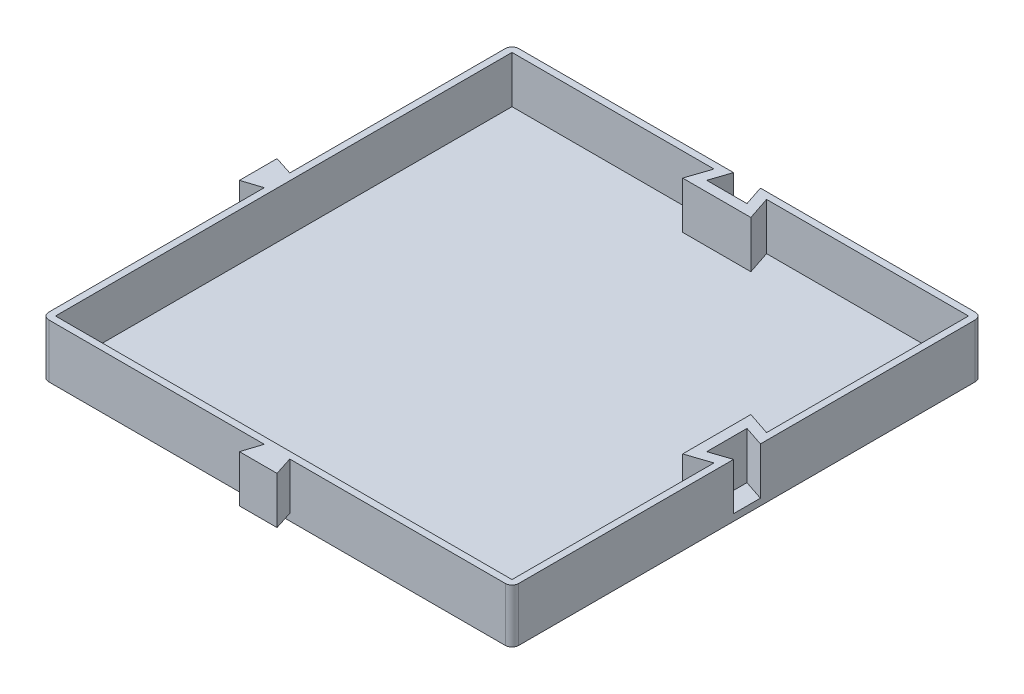
SolidWorks part; units mm, degrees
ref_plane "Front Plane" through (0, 0, 0) normal (0, 0, 1) x (1, 0, 0)
ref_plane "Top Plane" through (0, 0, 0) normal (0, 1, 0) x (1, 0, 0)
ref_plane "Right Plane" through (0, 0, 0) normal (1, 0, 0) x (0, 0, -1)
sketch "Sketch1" plane through (0, 0, 0) normal (0, 1, 0) x (1, 0, 0)
  line L1 (0, 0) -> (88.9, 0)
  line L2 (0, 0) -> (0, 88.9)
  line L3 (0, 88.9) -> (88.9, 88.9)
  line L4 (88.9, 0) -> (88.9, 88.9)
  dimension "D1" = 88.9
  dimension "D2" = 88.9
extrude "Base/Drain Tray" add sketch "Sketch1" along normal blind 10.16
sketch "Sketch2" plane through (0, 10.16, 0) normal (0, 1, 0) x (1, 0, 0)
  line L8 (1.27, 87.63) -> (1.27, 1.27)
  line L9 (1.27, 1.27) -> (87.63, 1.27)
  line L10 (87.63, 1.27) -> (87.63, 87.63)
  line L11 (87.63, 87.63) -> (1.27, 87.63)
  line L12 (1.27, 87.63) -> (1.27, 1.27)
  line L13 (1.27, 1.27) -> (87.63, 1.27)
  line L14 (87.63, 1.27) -> (87.63, 87.63)
  line L15 (87.63, 87.63) -> (1.27, 87.63)
  dimension "D1" = 1.27
extrude "Drain Tray Cutout" cut sketch "Sketch2" against normal blind 8.89
sketch "Sketch3" plane through (0, 1.27, 0) normal (0, 1, 0) x (1, 0, 0)
  line L8 (80.01, 80.01) -> (8.89, 80.01)
  line L9 (8.89, 80.01) -> (8.89, 8.89)
  line L10 (8.89, 8.89) -> (80.01, 8.89)
  line L11 (80.01, 8.89) -> (80.01, 80.01)
  line L12 (80.01, 80.01) -> (8.89, 80.01)
  line L13 (8.89, 80.01) -> (8.89, 8.89)
  line L14 (8.89, 8.89) -> (80.01, 8.89)
  line L15 (80.01, 8.89) -> (80.01, 80.01)
  dimension "D2" = 71.12
  dimension "D1" = 7.62
extrude "Body" add sketch "Sketch3" along normal blind 50.8
sketch "Sketch4" plane through (0, 52.07, 0) normal (0, 1, 0) x (1, 0, 0)
  line L8 (78.74, 10.16) -> (78.74, 78.74)
  line L9 (78.74, 78.74) -> (10.16, 78.74)
  line L10 (10.16, 78.74) -> (10.16, 10.16)
  line L11 (10.16, 10.16) -> (78.74, 10.16)
  line L12 (78.74, 10.16) -> (78.74, 78.74)
  line L13 (78.74, 78.74) -> (10.16, 78.74)
  line L14 (10.16, 78.74) -> (10.16, 10.16)
  line L15 (10.16, 10.16) -> (78.74, 10.16)
  dimension "D1" = 1.27
extrude "Body Cutout" cut sketch "Sketch4" against normal blind 50.8
ref_plane "Plane1" through (44.45, 0, 0) normal (-1, 0, 0) x (0, 0, 1)
sketch "Sketch5" plane through (78.74, 0, 0) normal (-1, 0, 0) x (0, 0, 1)
  line L0 (-78.74, 1.27) -> (-78.74, 5.08) construction
  line L1 (-78.74, 1.27) -> (-78.74, 52.07) construction
  line L2 (-78.74, 5.08) -> (-10.16, 5.08) construction
  line L3 (-10.16, 1.27) -> (-10.16, 52.07) construction
  line L4 (-10.16, 1.27) -> (-78.74, 1.27) construction
  line L5 (-64.77, 1.27) -> (-54.61, 1.27)
  line L6 (-64.77, 1.27) -> (-64.77, 5.08)
  line L7 (-64.77, 5.08) -> (-54.61, 5.08)
  line L8 (-54.61, 1.27) -> (-54.61, 5.08)
  line L10 (-34.29, 1.27) -> (-24.13, 1.27)
  line L11 (-34.29, 1.27) -> (-34.29, 5.08)
  line L12 (-34.29, 5.08) -> (-24.13, 5.08)
  line L13 (-24.13, 1.27) -> (-24.13, 5.08)
  point P18 (-59.69, 5.08)
  point P19 (-29.21, 5.08)
  dimension "D1" = 3.81
  dimension "D2" = 10.16
  dimension "D3" = 10.16
  dimension "D4" = 19.05
  dimension "D5" = 19.05
extrude "Drain Holes 1" [suppressed] cut sketch "Sketch5" along normal up to surface (71.12 mm away) from offset 1.27 offset against normal yes
ref_plane "Plane2" through (0, 0, -44.45) normal (0, 0, -1) x (-1, 0, 0)
sketch "Sketch6" plane through (0, 0, -10.16) normal (0, 0, -1) x (-1, 0, 0)
  line L0 (-78.74, 5.08) -> (-10.16, 5.08) construction
  line L1 (-78.74, 1.27) -> (-78.74, 52.07) construction
  line L2 (-10.16, 1.27) -> (-10.16, 52.07) construction
  line L3 (-10.16, 1.27) -> (-78.74, 1.27) construction
  line L5 (-64.77, 1.27) -> (-54.61, 1.27)
  line L6 (-64.77, 1.27) -> (-64.77, 5.08)
  line L7 (-64.77, 5.08) -> (-54.61, 5.08)
  line L8 (-54.61, 1.27) -> (-54.61, 5.08)
  line L9 (-34.29, 1.27) -> (-24.13, 1.27)
  line L10 (-34.29, 1.27) -> (-34.29, 5.08)
  line L11 (-34.29, 5.08) -> (-24.13, 5.08)
  line L12 (-24.13, 1.27) -> (-24.13, 5.08)
  point P16 (-59.69, 5.08)
  point P17 (-29.21, 5.08)
  dimension "D1" = 3.81
  dimension "D2" = 10.16
  dimension "D3" = 10.16
  dimension "D4" = 19.05
  dimension "D5" = 19.05
extrude "Drain Holes 2" [suppressed] cut sketch "Sketch6" along normal up to surface (71.12 mm away) from offset 1.27 offset against normal yes
fillet "Fillet1" radius 1.27 4 edges at (88.9, 5.08, 0) (0, 5.08, 0) (0, 5.08, -88.9) (88.9, 5.08, -88.9)
sketch "Sketch7" plane through (0, 1.27, 0) normal (0, 1, 0) x (1, 0, 0)
  line L0 (44.45, 88.9) -> (44.45, 0) construction
  line L1 (87.63, 88.9) -> (1.27, 88.9) construction
  line L2 (1.27, 0) -> (87.63, 0) construction
  line L3 (0, 44.45) -> (88.9, 44.45) construction
  line L4 (0, 87.63) -> (0, 1.27) construction
  line L5 (88.9, 1.27) -> (88.9, 87.63) construction
  line L6 (44.45, 88.9) -> (41.91, 88.9)
  line L7 (44.45, 88.9) -> (46.99, 88.9)
  line L8 (40.64, 85.09) -> (48.26, 85.09)
  line L9 (44.45, 85.09) -> (44.45, 85.5401) construction
  line L10 (41.91, 88.9) -> (40.64, 85.09)
  line L11 (46.99, 88.9) -> (48.26, 85.09)
  line L12 (48.363, 90.805) -> (50.903, 83.185)
  line L13 (37.997, 83.185) -> (50.903, 83.185)
  line L14 (40.537, 90.805) -> (37.997, 83.185)
  line L15 (44.45, 90.805) -> (40.537, 90.805)
  line L16 (44.45, 90.805) -> (48.363, 90.805)
  line L17 (41.91, 88.9) -> (39.902, 88.9)
  line L18 (46.99, 88.9) -> (48.998, 88.9)
  line M43 (87.63, 87.63) -> (1.27, 87.63)
  dimension "D1" = 2.54
  dimension "D2" = 2.54
  dimension "D3" = 7.62
  dimension "D4" = 3.81
  dimension "D5" = 1.905
extrude "Joining Slot" add sketch "Sketch7" along normal blind 8.89 contours L14 L13 L12 L11 L8 L10 M43 region at (44.45, 1.27, -84.8013)
sketch "Sketch8" plane through (0, 10.16, 0) normal (0, 1, 0) x (1, 0, 0)
  line L0 (40.64, 85.09) -> (41.4867, 87.63)
  line L1 (41.4867, 87.63) -> (41.91, 88.9)
  line L2 (87.63, 88.9) -> (1.27, 88.9) construction
  line L3 (40.64, 85.09) -> (48.26, 85.09)
  line L4 (48.26, 85.09) -> (47.4133, 87.63)
  line L5 (47.4133, 87.63) -> (46.99, 88.9)
  line L6 (46.99, 88.9) -> (41.91, 88.9)
extrude "Joining Cutout" cut sketch "Sketch8" against normal blind 8.89
sketch "Sketch10" plane through (0, 1.27, 0) normal (0, 1, 0) x (1, 0, 0)
  line L0 (39.4786, 87.63) -> (37.997, 83.185)
  line L1 (37.997, 83.185) -> (50.903, 83.185)
  line L2 (50.903, 83.185) -> (49.4214, 87.63)
  line L3 (41.91, 88.9) -> (40.64, 85.09)
  line L4 (40.64, 85.09) -> (48.26, 85.09)
  line L5 (48.26, 85.09) -> (46.99, 88.9)
  line L6 (46.99, 88.9) -> (41.91, 88.9)
  line L7 (44.45, 78.74) -> (44.45, 10.16) construction
  line L8 (78.74, 78.74) -> (10.16, 78.74) construction
  line L9 (10.16, 10.16) -> (78.74, 10.16) construction
  line L10 (44.45, 44.45) -> (10.16, 44.45) construction
  line L11 (10.16, 78.74) -> (10.16, 10.16) construction
  line L12 (87.63, 49.4214) -> (83.185, 50.903)
  line L13 (83.185, 50.903) -> (83.185, 37.997)
  line L14 (83.185, 37.997) -> (87.63, 39.4786)
  line L15 (44.45, 44.45) -> (50.903, 83.185) construction
  line L16 (44.45, 44.45) -> (83.185, 37.997) construction
  line L17 (87.63, 49.4214) -> (87.63, 39.4786)
  dimension "D2" = 90
  dimension "D1" = 2
extrude "Joining Slot 2" add sketch "Sketch10" along normal blind 8.89 contours L17 L12 L13 L14 region at (85.3114, 1.27, -44.45)
sketch "Sketch12" plane through (0, 1.27, 0) normal (0, 1, 0) x (1, 0, 0)
  line L0 (41.91, 88.9) -> (40.64, 85.09)
  line L1 (40.64, 85.09) -> (48.26, 85.09)
  line L2 (48.26, 85.09) -> (46.99, 88.9)
  line L3 (46.99, 88.9) -> (41.91, 88.9)
  line L4 (44.45, 78.74) -> (44.45, 10.16) construction
  line L5 (78.74, 78.74) -> (10.16, 78.74) construction
  line L6 (10.16, 10.16) -> (78.74, 10.16) construction
  line L7 (44.45, 44.45) -> (10.16, 44.45) construction
  line L8 (10.16, 78.74) -> (10.16, 10.16) construction
  line L9 (88.9, 41.91) -> (88.9, 46.99)
  line L10 (88.9, 46.99) -> (85.09, 48.26)
  line L11 (85.09, 48.26) -> (85.09, 40.64)
  line L12 (85.09, 40.64) -> (88.9, 41.91)
  line L13 (44.45, 44.45) -> (48.26, 85.09) construction
  line L14 (44.45, 44.45) -> (85.09, 40.64) construction
  dimension "D2" = 90
  dimension "D1" = 2
extrude "Joining Cutout 2" cut sketch "Sketch12" along normal blind 8.89 contours L9 L10 L11 L12
sketch "Sketch13" plane through (0, 1.27, 0) normal (0, 1, 0) x (1, 0, 0)
  line L0 (44.45, 88.9) -> (44.45, 0) construction
  line L1 (46.99, 88.9) -> (41.91, 88.9) construction
  line L2 (1.27, 0) -> (87.63, 0) construction
  line L3 (44.45, 44.45) -> (0, 44.45) construction
  line L4 (0, 87.63) -> (0, 1.27) construction
  line L5 (42.037, 0) -> (46.863, 0)
  line L6 (44.45, 0) -> (44.45, -3.556) construction
  line L7 (40.894, -3.556) -> (44.45, -3.556)
  line L8 (44.45, -3.556) -> (48.006, -3.556)
  line L9 (42.037, 0) -> (40.894, -3.556)
  line L10 (46.863, 0) -> (48.006, -3.556)
  line L16 (0, 46.863) -> (0, 42.037)
  line L17 (0, 46.863) -> (-3.556, 48.006)
  line L18 (0, 42.037) -> (-3.556, 40.894)
  line L19 (-3.556, 44.45) -> (-3.556, 40.894)
  line L20 (-3.556, 48.006) -> (-3.556, 44.45)
  line L21 (44.45, 44.45) -> (42.037, 0) construction
  line L22 (44.45, 44.45) -> (0, 46.863) construction
  dimension "D1" = 4.826
  dimension "D2" = 7.112
  dimension "D3" = 3.556
  dimension "D5" = 90
  dimension "D4" = 2
extrude "Boss-Extrude3" add sketch "Sketch13" along normal blind 8.89
sketch "Sketch14" plane through (0, 52.07, 0) normal (0, 1, 0) x (1, 0, 0)
  line L1 (8.89, 80.01) -> (80.01, 80.01)
  line L2 (8.89, 80.01) -> (8.89, 8.89)
  line L3 (8.89, 8.89) -> (80.01, 8.89)
  line L4 (80.01, 80.01) -> (80.01, 8.89)
extrude "Cut-Extrude2" cut sketch "Sketch14" against normal up to surface (50.8 mm away) up to face at (44.45, 1.27, -44.45)
